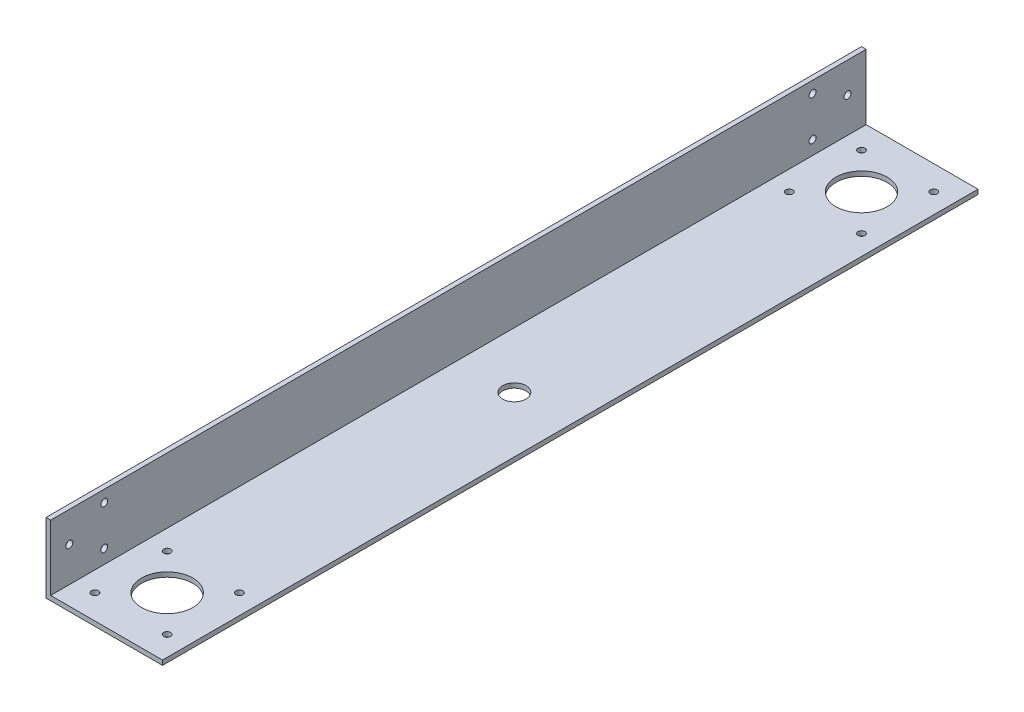
SolidWorks part; units mm, degrees
ref_plane "Front Plane" through (0, 0, 0) normal (0, 0, 1) x (1, 0, 0)
ref_plane "Top Plane" through (0, 0, 0) normal (0, 1, 0) x (1, 0, 0)
ref_plane "Right Plane" through (0, 0, 0) normal (1, 0, 0) x (0, 0, -1)
sketch "Sketch1" plane through (0, 0, 0) normal (0, 0, 1) x (1, 0, 0)
  line L0 (0, 0) -> (0, 30)
  line L1 (0, 30) -> (2, 30)
  line L2 (2, 30) -> (2, 2)
  line L3 (2, 2) -> (50, 2)
  line L4 (50, 2) -> (50, 0)
  line L5 (50, 0) -> (0, 0)
extrude "Boss-Extrude1" add sketch "Sketch1" along normal blind 350
sketch "Sketch6" plane through (0, 2, 0) normal (0, 1, 0) x (1, 0, 0)
  circle A0 centre (41.5, -339.5) radius 1.5
  circle A1 centre (10.5, -308.5) radius 1.5
  circle A2 centre (10.5, -339.5) radius 1.5
  circle A3 centre (41.5, -308.5) radius 1.5
extrude "Cut-Extrude3" cut sketch "Sketch6" against normal through all
sketch "Sketch7" plane through (0, 2, 0) normal (0, 1, 0) x (1, 0, 0)
  circle A0 centre (26, -324) radius 11
extrude "Cut-Extrude4" cut sketch "Sketch7" against normal through all
sketch "Sketch8" plane through (0, 0, 0) normal (0, -1, 0) x (-1, 0, 0)
  circle A0 centre (-26, -26) radius 11
extrude "Cut-Extrude5" cut sketch "Sketch8" against normal through all
sketch "Sketch9" plane through (0, 0, 0) normal (0, -1, 0) x (1, 0, 0)
  circle A0 centre (41.5, 41.5) radius 1.5
  circle A1 centre (10.5, 41.5) radius 1.5
  circle A2 centre (10.5, 10.5) radius 1.5
  circle A3 centre (41.5, 10.5) radius 1.5
extrude "Cut-Extrude6" cut sketch "Sketch9" against normal through all
sketch "Sketch10" plane through (0, 0, 0) normal (0, -1, 0) x (1, 0, 0)
  circle A0 centre (26, 175) radius 5
extrude "Cut-Extrude7" cut sketch "Sketch10" against normal through all
hole_wizard "Ø3.0 (3) Diameter Hole1" positions "Sketch11" profile "Sketch12" hole size "Ø3.0" standard "ISO"
sketch "Sketch11" plane through (0, 141.68, 221.138) normal (-1, 0, 0) x (0, 0, 1)
  point P0 (105.862, -133.68)
  point P1 (120.862, -124.68)
  point P2 (105.862, -116.68)
sketch "Sketch12" plane through (0, 8, 327) normal (0, 1, 0) x (0, 0, 1)
  line L0 (0, 0) -> (0, 1.999)
  line L1 (0, 1.999) -> (1.5, 1.999)
  line L2 (1.5, 1.999) -> (1.5, 0)
  line L3 (1.5, 0) -> (0, 0)
  line L4 (0, -6.35) -> (0, 107.95) construction
  dimension "Thru Hole Dia." = 3
  dimension "Thru Hole Depth" = 1.999
hole_wizard "Ø3.0 (3) Diameter Hole2" positions "Sketch13" profile "Sketch14" hole size "Ø3.0" standard "ISO"
sketch "Sketch13" plane through (0, 141.68, 221.138) normal (-1, 0, 0) x (0, 0, 1)
  point P0 (-198.138, -133.68)
  point P1 (-213.138, -124.7112)
  point P2 (-198.138, -116.68)
sketch "Sketch14" plane through (0, 8, 23) normal (0, 1, 0) x (0, 0, 1)
  line L0 (0, 0) -> (0, 1.999)
  line L1 (0, 1.999) -> (1.5, 1.999)
  line L2 (1.5, 1.999) -> (1.5, 0)
  line L3 (1.5, 0) -> (0, 0)
  line L4 (0, -6.35) -> (0, 107.95) construction
  dimension "Thru Hole Dia." = 3
  dimension "Thru Hole Depth" = 1.999
